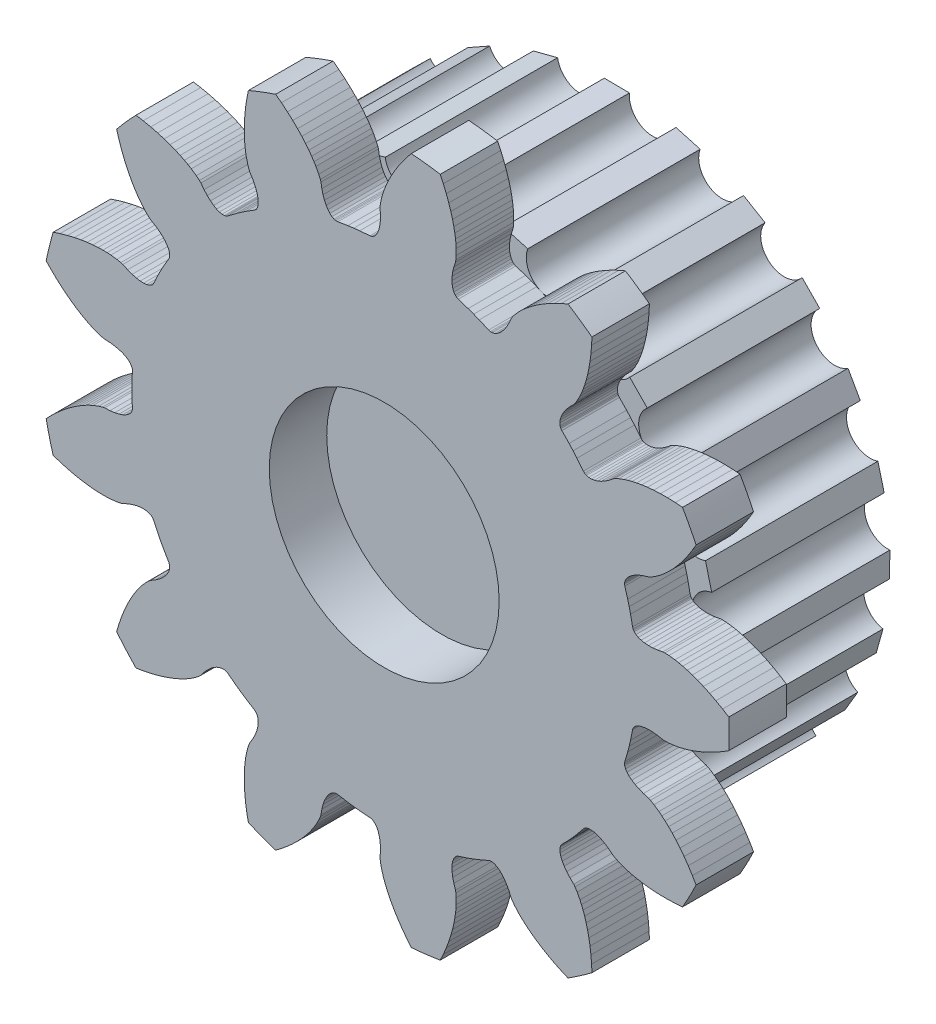
SolidWorks part; units mm, degrees
ref_plane "Front Plane" through (0, 0, 0) normal (0, 0, 1) x (1, 0, 0)
ref_plane "Top Plane" through (0, 0, 0) normal (0, 1, 0) x (1, 0, 0)
ref_plane "Right Plane" through (0, 0, 0) normal (1, 0, 0) x (0, 0, -1)
sketch "Model" plane through (0, 0, 0) normal (0, 0, 1) x (1, 0, 0)
  line L0 (54.9037, -18.3182) -> (55.119, -17.6838)
  line L1 (55.119, -17.6838) -> (55.345, -17.0995)
  line L2 (55.345, -17.0995) -> (55.5777, -16.5655)
  line L3 (55.5777, -16.5655) -> (55.8147, -16.0783)
  line L4 (55.8147, -16.0783) -> (56.0515, -15.6392)
  line L5 (56.0515, -15.6392) -> (56.2838, -15.2487)
  line L6 (56.2838, -15.2487) -> (56.5097, -14.9028)
  line L7 (56.5097, -14.9028) -> (56.7244, -14.6022)
  line L8 (56.7244, -14.6022) -> (56.9247, -14.3453)
  line L9 (56.9247, -14.3453) -> (57.2703, -13.9536)
  line L10 (57.2703, -13.9536) -> (57.526, -13.708)
  line L11 (57.526, -13.708) -> (57.6679, -13.5941)
  line L12 (57.6679, -13.5941) -> (58.066, -13.3611)
  line L13 (58.066, -13.3611) -> (58.4092, -13.1204)
  line L14 (58.4092, -13.1204) -> (58.6978, -12.8763)
  line L15 (58.6978, -12.8763) -> (58.932, -12.6328)
  line L16 (58.932, -12.6328) -> (59.1126, -12.3942)
  line L17 (59.1126, -12.3942) -> (59.2403, -12.1644)
  line L18 (59.2403, -12.1644) -> (59.3164, -11.9475)
  line L19 (59.3164, -11.9475) -> (59.3421, -11.7472)
  line L20 (59.3421, -11.7472) -> (59.3367, -11.6545)
  line L21 (59.3367, -11.6545) -> (59.3192, -11.5674)
  line L22 (59.3192, -11.5674) -> (59.2607, -11.4299)
  line L23 (59.2607, -11.4299) -> (58.8102, -10.6563)
  line L24 (58.8102, -10.6563) -> (58.5642, -10.2007)
  line L25 (58.5642, -10.2007) -> (58.329, -9.7394)
  line L26 (58.329, -9.7394) -> (57.9483, -8.9292)
  line L27 (57.9483, -8.9292) -> (57.8683, -8.8029)
  line L28 (57.8683, -8.8029) -> (57.8065, -8.7391)
  line L29 (57.8065, -8.7391) -> (57.7334, -8.6819)
  line L30 (57.7334, -8.6819) -> (57.5539, -8.5894)
  line L31 (57.5539, -8.5894) -> (57.3321, -8.5288)
  line L32 (57.3321, -8.5288) -> (57.0705, -8.5034)
  line L33 (57.0705, -8.5034) -> (56.7715, -8.5164)
  line L34 (56.7715, -8.5164) -> (56.4381, -8.5709)
  line L35 (56.4381, -8.5709) -> (56.0733, -8.6697)
  line L36 (56.0733, -8.6697) -> (55.6803, -8.8154)
  line L37 (55.6803, -8.8154) -> (55.2623, -9.0107)
  line L38 (55.2623, -9.0107) -> (55.088, -9.0628)
  line L39 (55.088, -9.0628) -> (54.7406, -9.1337)
  line L40 (54.7406, -9.1337) -> (54.2219, -9.1956)
  line L41 (54.2219, -9.1956) -> (53.8967, -9.2145)
  line L42 (53.8967, -9.2145) -> (53.5274, -9.2205)
  line L43 (53.5274, -9.2205) -> (53.1144, -9.2099)
  line L44 (53.1144, -9.2099) -> (52.6611, -9.1792)
  line L45 (52.6611, -9.1792) -> (52.1651, -9.1246)
  line L46 (52.1651, -9.1246) -> (51.6295, -9.0429)
  line L47 (51.6295, -9.0429) -> (51.0579, -8.9311)
  line L48 (51.0579, -8.9311) -> (50.4486, -8.7851)
  line L49 (50.4486, -8.7851) -> (49.8043, -8.6019)
  line L50 (49.8043, -8.6019) -> (49.2012, -8.4037)
  line L51 (48.5945, -5.9424) -> (49.0364, -5.4866)
  line L52 (49.0364, -5.4866) -> (49.5218, -5.0249)
  line L53 (49.5218, -5.0249) -> (49.9935, -4.6126)
  line L54 (49.9935, -4.6126) -> (50.4476, -4.2479)
  line L55 (50.4476, -4.2479) -> (50.8839, -3.9266)
  line L56 (50.8839, -3.9266) -> (51.2977, -3.6479)
  line L57 (51.2977, -3.6479) -> (51.6848, -3.41)
  line L58 (51.6848, -3.41) -> (52.0456, -3.2087)
  line L59 (52.0456, -3.2087) -> (52.3754, -3.0423)
  line L60 (52.3754, -3.0423) -> (52.6721, -2.9079)
  line L61 (52.6721, -2.9079) -> (53.1602, -2.7217)
  line L62 (53.1602, -2.7217) -> (53.5007, -2.623)
  line L63 (53.5007, -2.623) -> (53.6793, -2.5882)
  line L64 (53.6793, -2.5882) -> (54.1401, -2.5668)
  line L65 (54.1401, -2.5668) -> (54.5559, -2.5132)
  line L66 (54.5559, -2.5132) -> (54.9248, -2.4312)
  line L67 (54.9248, -2.4312) -> (55.2454, -2.3245)
  line L68 (55.2454, -2.3245) -> (55.5161, -2.1971)
  line L69 (55.5161, -2.1971) -> (55.736, -2.053)
  line L70 (55.736, -2.053) -> (55.9042, -1.8962)
  line L71 (55.9042, -1.8962) -> (56.0201, -1.7309)
  line L72 (56.0201, -1.7309) -> (56.0583, -1.6463)
  line L73 (56.0583, -1.6463) -> (56.0834, -1.5611)
  line L74 (56.0834, -1.5611) -> (56.0954, -1.4121)
  line L75 (56.0954, -1.4121) -> (56.056, -0.5178)
  line L76 (56.056, -0.5178) -> (56.05, 0)
  line L77 (56.05, 0) -> (56.056, 0.5178)
  line L78 (56.056, 0.5178) -> (56.0954, 1.4121)
  line L79 (56.0954, 1.4121) -> (56.0834, 1.5611)
  line L80 (56.0834, 1.5611) -> (56.0583, 1.6463)
  line L81 (56.0583, 1.6463) -> (56.0201, 1.7309)
  line L82 (56.0201, 1.7309) -> (55.9042, 1.8962)
  line L83 (55.9042, 1.8962) -> (55.736, 2.053)
  line L84 (55.736, 2.053) -> (55.5161, 2.1971)
  line L85 (55.5161, 2.1971) -> (55.2454, 2.3245)
  line L86 (55.2454, 2.3245) -> (54.9248, 2.4312)
  line L87 (54.9248, 2.4312) -> (54.5559, 2.5132)
  line L88 (54.5559, 2.5132) -> (54.1401, 2.5668)
  line L89 (54.1401, 2.5668) -> (53.6793, 2.5882)
  line L90 (53.6793, 2.5882) -> (53.5007, 2.623)
  line L91 (53.5007, 2.623) -> (53.1602, 2.7217)
  line L92 (53.1602, 2.7217) -> (52.6721, 2.9079)
  line L93 (52.6721, 2.9079) -> (52.3754, 3.0423)
  line L94 (52.3754, 3.0423) -> (52.0456, 3.2087)
  line L95 (52.0456, 3.2087) -> (51.6848, 3.41)
  line L96 (51.6848, 3.41) -> (51.2977, 3.6479)
  line L97 (51.2977, 3.6479) -> (50.8839, 3.9266)
  line L98 (50.8839, 3.9266) -> (50.4476, 4.2479)
  line L99 (50.4476, 4.2479) -> (49.9935, 4.6126)
  line L100 (49.9935, 4.6126) -> (49.5218, 5.0249)
  line L101 (49.5218, 5.0249) -> (49.0364, 5.4866)
  line L102 (49.0364, 5.4866) -> (48.5945, 5.9424)
  line L103 (49.2012, 8.4037) -> (49.8043, 8.6019)
  line L104 (49.8043, 8.6019) -> (50.4486, 8.7851)
  line L105 (50.4486, 8.7851) -> (51.0579, 8.9311)
  line L106 (51.0579, 8.9311) -> (51.6295, 9.0429)
  line L107 (51.6295, 9.0429) -> (52.1651, 9.1246)
  line L108 (52.1651, 9.1246) -> (52.6611, 9.1792)
  line L109 (52.6611, 9.1792) -> (53.1144, 9.2099)
  line L110 (53.1144, 9.2099) -> (53.5274, 9.2205)
  line L111 (53.5274, 9.2205) -> (53.8967, 9.2145)
  line L112 (53.8967, 9.2145) -> (54.2219, 9.1956)
  line L113 (54.2219, 9.1956) -> (54.7406, 9.1337)
  line L114 (54.7406, 9.1337) -> (55.088, 9.0628)
  line L115 (55.088, 9.0628) -> (55.2623, 9.0107)
  line L116 (55.2623, 9.0107) -> (55.6803, 8.8154)
  line L117 (55.6803, 8.8154) -> (56.0733, 8.6697)
  line L118 (56.0733, 8.6697) -> (56.4381, 8.5709)
  line L119 (56.4381, 8.5709) -> (56.7715, 8.5164)
  line L120 (56.7715, 8.5164) -> (57.0705, 8.5034)
  line L121 (57.0705, 8.5034) -> (57.3321, 8.5288)
  line L122 (57.3321, 8.5288) -> (57.5539, 8.5894)
  line L123 (57.5539, 8.5894) -> (57.7334, 8.6819)
  line L124 (57.7334, 8.6819) -> (57.8065, 8.7391)
  line L125 (57.8065, 8.7391) -> (57.8683, 8.8029)
  line L126 (57.8683, 8.8029) -> (57.9483, 8.9292)
  line L127 (57.9483, 8.9292) -> (58.329, 9.7394)
  line L128 (58.329, 9.7394) -> (58.5642, 10.2007)
  line L129 (58.5642, 10.2007) -> (58.8102, 10.6563)
  line L130 (58.8102, 10.6563) -> (59.2607, 11.4299)
  line L131 (59.2607, 11.4299) -> (59.3192, 11.5674)
  line L132 (59.3192, 11.5674) -> (59.3367, 11.6545)
  line L133 (59.3367, 11.6545) -> (59.3421, 11.7472)
  line L134 (59.3421, 11.7472) -> (59.3164, 11.9475)
  line L135 (59.3164, 11.9475) -> (59.2403, 12.1644)
  line L136 (59.2403, 12.1644) -> (59.1126, 12.3942)
  line L137 (59.1126, 12.3942) -> (58.932, 12.6328)
  line L138 (58.932, 12.6328) -> (58.6978, 12.8763)
  line L139 (58.6978, 12.8763) -> (58.4092, 13.1204)
  line L140 (58.4092, 13.1204) -> (58.066, 13.3611)
  line L141 (58.066, 13.3611) -> (57.6679, 13.5941)
  line L142 (57.6679, 13.5941) -> (57.526, 13.708)
  line L143 (57.526, 13.708) -> (57.2703, 13.9536)
  line L144 (57.2703, 13.9536) -> (56.9247, 14.3453)
  line L145 (56.9247, 14.3453) -> (56.7244, 14.6022)
  line L146 (56.7244, 14.6022) -> (56.5097, 14.9028)
  line L147 (56.5097, 14.9028) -> (56.2838, 15.2487)
  line L148 (56.2838, 15.2487) -> (56.0515, 15.6392)
  line L149 (56.0515, 15.6392) -> (55.8147, 16.0783)
  line L150 (55.8147, 16.0783) -> (55.5777, 16.5655)
  line L151 (55.5777, 16.5655) -> (55.345, 17.0995)
  line L152 (55.345, 17.0995) -> (55.119, 17.6838)
  line L153 (55.119, 17.6838) -> (54.9037, 18.3182)
  line L154 (54.9037, 18.3182) -> (54.7243, 18.9271)
  line L155 (56.4053, 20.8246) -> (57.0315, 20.7198)
  line L156 (57.0315, 20.7198) -> (57.6871, 20.5826)
  line L157 (57.6871, 20.5826) -> (58.2944, 20.4287)
  line L158 (58.2944, 20.4287) -> (58.8525, 20.2621)
  line L159 (58.8525, 20.2621) -> (59.3648, 20.0855)
  line L160 (59.3648, 20.0855) -> (59.8293, 19.9033)
  line L161 (59.8293, 19.9033) -> (60.2449, 19.7199)
  line L162 (60.2449, 19.7199) -> (60.6155, 19.5373)
  line L163 (60.6155, 19.5373) -> (60.9398, 19.3604)
  line L164 (60.9398, 19.3604) -> (61.219, 19.1925)
  line L165 (61.219, 19.1925) -> (61.6495, 18.8967)
  line L166 (61.6495, 18.8967) -> (61.9241, 18.6724)
  line L167 (61.9241, 18.6724) -> (62.0542, 18.5453)
  line L168 (62.0542, 18.5453) -> (62.3336, 18.1782)
  line L169 (62.3336, 18.1782) -> (62.6139, 17.8664)
  line L170 (62.6139, 17.8664) -> (62.891, 17.6094)
  line L171 (62.891, 17.6094) -> (63.1609, 17.4062)
  line L172 (63.1609, 17.4062) -> (63.4195, 17.2558)
  line L173 (63.4195, 17.2558) -> (63.663, 17.1567)
  line L174 (63.663, 17.1567) -> (63.8876, 17.1073)
  line L175 (63.8876, 17.1073) -> (64.0895, 17.1058)
  line L176 (64.0895, 17.1058) -> (64.1808, 17.1224)
  line L177 (64.1808, 17.1224) -> (64.2652, 17.1503)
  line L178 (64.2652, 17.1503) -> (64.3947, 17.225)
  line L179 (64.3947, 17.225) -> (65.1083, 17.7654)
  line L180 (65.1083, 17.7654) -> (65.531, 18.0645)
  line L181 (65.531, 18.0645) -> (65.9605, 18.3536)
  line L182 (65.9605, 18.3536) -> (66.7189, 18.8292)
  line L183 (66.7189, 18.8292) -> (66.8347, 18.9238)
  line L184 (66.8347, 18.9238) -> (66.8906, 18.9928)
  line L185 (66.8906, 18.9928) -> (66.9385, 19.0724)
  line L186 (66.9385, 19.0724) -> (67.0087, 19.2617)
  line L187 (67.0087, 19.2617) -> (67.0422, 19.4891)
  line L188 (67.0422, 19.4891) -> (67.0359, 19.752)
  line L189 (67.0359, 19.752) -> (66.9869, 20.0471)
  line L190 (66.9869, 20.0471) -> (66.8926, 20.3715)
  line L191 (66.8926, 20.3715) -> (66.7506, 20.7218)
  line L192 (66.7506, 20.7218) -> (66.5585, 21.0944)
  line L193 (66.5585, 21.0944) -> (66.3143, 21.4858)
  line L194 (66.3143, 21.4858) -> (66.2416, 21.6526)
  line L195 (66.2416, 21.6526) -> (66.1293, 21.9888)
  line L196 (66.1293, 21.9888) -> (66.0053, 22.4963)
  line L197 (66.0053, 22.4963) -> (65.9473, 22.8169)
  line L198 (65.9473, 22.8169) -> (65.8969, 23.1828)
  line L199 (65.8969, 23.1828) -> (65.8577, 23.5941)
  line L200 (65.8577, 23.5941) -> (65.8335, 24.0478)
  line L201 (65.8335, 24.0478) -> (65.8278, 24.5467)
  line L202 (65.8278, 24.5467) -> (65.8444, 25.0882)
  line L203 (65.8444, 25.0882) -> (65.8865, 25.6691)
  line L204 (65.8865, 25.6691) -> (65.958, 26.2916)
  line L205 (65.958, 26.2916) -> (66.0622, 26.9533)
  line L206 (66.0622, 26.9533) -> (66.1863, 27.5759)
  line L207 (68.5565, 28.4748) -> (69.0623, 28.0911)
  line L208 (69.0623, 28.0911) -> (69.5791, 27.6649)
  line L209 (69.5791, 27.6649) -> (70.0453, 27.2463)
  line L210 (70.0453, 27.2463) -> (70.462, 26.8395)
  line L211 (70.462, 26.8395) -> (70.8335, 26.4451)
  line L212 (70.8335, 26.4451) -> (71.1601, 26.0679)
  line L213 (71.1601, 26.0679) -> (71.4429, 25.7123)
  line L214 (71.4429, 25.7123) -> (71.6863, 25.3784)
  line L215 (71.6863, 25.3784) -> (71.8911, 25.0711)
  line L216 (71.8911, 25.0711) -> (72.0604, 24.7927)
  line L217 (72.0604, 24.7927) -> (72.3041, 24.3306)
  line L218 (72.3041, 24.3306) -> (72.443, 24.0045)
  line L219 (72.443, 24.0045) -> (72.4991, 23.8314)
  line L220 (72.4991, 23.8314) -> (72.5759, 23.3765)
  line L221 (72.5759, 23.3765) -> (72.6792, 22.9702)
  line L222 (72.6792, 22.9702) -> (72.8051, 22.6139)
  line L223 (72.8051, 22.6139) -> (72.9497, 22.3085)
  line L224 (72.9497, 22.3085) -> (73.1088, 22.0551)
  line L225 (73.1088, 22.0551) -> (73.2784, 21.8542)
  line L226 (73.2784, 21.8542) -> (73.4542, 21.7061)
  line L227 (73.4542, 21.7061) -> (73.6323, 21.611)
  line L228 (73.6323, 21.611) -> (73.7209, 21.5833)
  line L229 (73.7209, 21.5833) -> (73.8085, 21.5687)
  line L230 (73.8085, 21.5687) -> (73.9579, 21.5746)
  line L231 (73.9579, 21.5746) -> (74.841, 21.7216)
  line L232 (74.841, 21.7216) -> (75.3542, 21.79)
  line L233 (75.3542, 21.79) -> (75.8689, 21.8464)
  line L234 (75.8689, 21.8464) -> (76.7615, 21.9151)
  line L235 (76.7615, 21.9151) -> (76.9079, 21.945)
  line L236 (76.9079, 21.945) -> (76.9895, 21.9801)
  line L237 (76.9895, 21.9801) -> (77.0689, 22.0283)
  line L238 (77.0689, 22.0283) -> (77.2191, 22.1633)
  line L239 (77.2191, 22.1633) -> (77.3544, 22.3491)
  line L240 (77.3544, 22.3491) -> (77.4709, 22.5848)
  line L241 (77.4709, 22.5848) -> (77.5648, 22.8689)
  line L242 (77.5648, 22.8689) -> (77.6321, 23.2)
  line L243 (77.6321, 23.2) -> (77.669, 23.5761)
  line L244 (77.669, 23.5761) -> (77.6721, 23.9953)
  line L245 (77.6721, 23.9953) -> (77.6378, 24.4554)
  line L246 (77.6378, 24.4554) -> (77.6509, 24.6368)
  line L247 (77.6509, 24.6368) -> (77.7077, 24.9868)
  line L248 (77.7077, 24.9868) -> (77.8338, 25.4937)
  line L249 (77.8338, 25.4937) -> (77.9314, 25.8045)
  line L250 (77.9314, 25.8045) -> (78.0568, 26.1519)
  line L251 (78.0568, 26.1519) -> (78.2132, 26.5343)
  line L252 (78.2132, 26.5343) -> (78.4026, 26.9473)
  line L253 (78.4026, 26.9473) -> (78.6295, 27.3917)
  line L254 (78.6295, 27.3917) -> (78.8958, 27.8635)
  line L255 (78.8958, 27.8635) -> (79.2031, 28.3583)
  line L256 (79.2031, 28.3583) -> (79.5556, 28.8762)
  line L257 (79.5556, 28.8762) -> (79.9554, 29.4137)
  line L258 (79.9554, 29.4137) -> (80.3546, 29.9073)
  line L259 (82.8711, 29.6018) -> (83.1406, 29.027)
  line L260 (83.1406, 29.027) -> (83.4001, 28.4094)
  line L261 (83.4001, 28.4094) -> (83.6184, 27.8222)
  line L262 (83.6184, 27.8222) -> (83.7984, 27.2683)
  line L263 (83.7984, 27.2683) -> (83.9441, 26.7464)
  line L264 (83.9441, 26.7464) -> (84.058, 26.2606)
  line L265 (84.058, 26.2606) -> (84.1431, 25.8143)
  line L266 (84.1431, 25.8143) -> (84.2034, 25.4056)
  line L267 (84.2034, 25.4056) -> (84.242, 25.0383)
  line L268 (84.242, 25.0383) -> (84.2624, 24.7131)
  line L269 (84.2624, 24.7131) -> (84.2635, 24.1907)
  line L270 (84.2635, 24.1907) -> (84.235, 23.8373)
  line L271 (84.235, 23.8373) -> (84.2043, 23.6581)
  line L272 (84.2043, 23.6581) -> (84.0608, 23.2196)
  line L273 (84.0608, 23.2196) -> (83.9635, 22.8118)
  line L274 (83.9635, 22.8118) -> (83.9094, 22.4377)
  line L275 (83.9094, 22.4377) -> (83.8955, 22.1002)
  line L276 (83.8955, 22.1002) -> (83.9186, 21.8019)
  line L277 (83.9186, 21.8019) -> (83.9753, 21.5452)
  line L278 (83.9753, 21.5452) -> (84.0623, 21.3323)
  line L279 (84.0623, 21.3323) -> (84.1758, 21.1653)
  line L280 (84.1758, 21.1653) -> (84.2413, 21.0996)
  line L281 (84.2413, 21.0996) -> (84.3121, 21.046)
  line L282 (84.3121, 21.046) -> (84.4472, 20.9818)
  line L283 (84.4472, 20.9818) -> (85.2973, 20.7016)
  line L284 (85.2973, 20.7016) -> (85.7836, 20.5236)
  line L285 (85.7836, 20.5236) -> (86.2655, 20.3344)
  line L286 (86.2655, 20.3344) -> (87.0878, 19.9804)
  line L287 (87.0878, 19.9804) -> (87.2314, 19.9389)
  line L288 (87.2314, 19.9389) -> (87.3199, 19.932)
  line L289 (87.3199, 19.932) -> (87.4126, 19.9378)
  line L290 (87.4126, 19.9378) -> (87.6083, 19.9875)
  line L291 (87.6083, 19.9875) -> (87.8145, 20.0892)
  line L292 (87.8145, 20.0892) -> (88.0272, 20.2437)
  line L293 (88.0272, 20.2437) -> (88.2423, 20.4517)
  line L294 (88.2423, 20.4517) -> (88.4558, 20.7135)
  line L295 (88.4558, 20.7135) -> (88.6633, 21.0294)
  line L296 (88.6633, 21.0294) -> (88.8609, 21.3992)
  line L297 (88.8609, 21.3992) -> (89.0442, 21.8225)
  line L298 (89.0442, 21.8225) -> (89.1401, 21.9771)
  line L299 (89.1401, 21.9771) -> (89.3531, 22.2605)
  line L300 (89.3531, 22.2605) -> (89.7003, 22.6508)
  line L301 (89.7003, 22.6508) -> (89.9312, 22.8806)
  line L302 (89.9312, 22.8806) -> (90.2037, 23.13)
  line L303 (90.2037, 23.13) -> (90.5199, 23.3959)
  line L304 (90.5199, 23.3959) -> (90.8796, 23.6735)
  line L305 (90.8796, 23.6735) -> (91.2869, 23.9616)
  line L306 (91.2869, 23.9616) -> (91.742, 24.2556)
  line L307 (91.742, 24.2556) -> (92.2441, 24.5509)
  line L308 (92.2441, 24.5509) -> (92.7969, 24.8457)
  line L309 (92.7969, 24.8457) -> (93.4007, 25.1359)
  line L310 (93.4007, 25.1359) -> (93.9836, 25.3874)
  line L311 (96.0698, 23.9474) -> (96.0413, 23.3132)
  line L312 (96.0413, 23.3132) -> (95.9841, 22.6457)
  line L313 (95.9841, 22.6457) -> (95.9045, 22.0243)
  line L314 (95.9045, 22.0243) -> (95.8064, 21.4502)
  line L315 (95.8064, 21.4502) -> (95.6929, 20.9204)
  line L316 (95.6929, 20.9204) -> (95.568, 20.4373)
  line L317 (95.568, 20.4373) -> (95.4359, 20.0026)
  line L318 (95.4359, 20.0026) -> (95.2994, 19.6127)
  line L319 (95.2994, 19.6127) -> (95.1629, 19.2695)
  line L320 (95.1629, 19.2695) -> (95.0299, 18.9721)
  line L321 (95.0299, 18.9721) -> (94.7881, 18.509)
  line L322 (94.7881, 18.509) -> (94.5986, 18.2094)
  line L323 (94.5986, 18.2094) -> (94.488, 18.0649)
  line L324 (94.488, 18.0649) -> (94.1573, 17.7433)
  line L325 (94.1573, 17.7433) -> (93.8816, 17.4275)
  line L326 (93.8816, 17.4275) -> (93.6598, 17.1214)
  line L327 (93.6598, 17.1214) -> (93.4907, 16.829)
  line L328 (93.4907, 16.829) -> (93.3725, 16.5541)
  line L329 (93.3725, 16.5541) -> (93.3035, 16.3004)
  line L330 (93.3035, 16.3004) -> (93.2815, 16.0716)
  line L331 (93.2815, 16.0716) -> (93.3044, 15.871)
  line L332 (93.3044, 15.871) -> (93.3319, 15.7823)
  line L333 (93.3319, 15.7823) -> (93.3697, 15.7019)
  line L334 (93.3697, 15.7019) -> (93.4594, 15.5824)
  line L335 (93.4594, 15.5824) -> (94.082, 14.9391)
  line L336 (94.082, 14.9391) -> (94.4298, 14.5555)
  line L337 (94.4298, 14.5555) -> (94.7686, 14.164)
  line L338 (94.7686, 14.164) -> (95.3322, 13.4685)
  line L339 (95.3322, 13.4685) -> (95.44, 13.3649)
  line L340 (95.44, 13.3649) -> (95.5153, 13.3178)
  line L341 (95.5153, 13.3178) -> (95.6, 13.2798)
  line L342 (95.6, 13.2798) -> (95.7964, 13.2329)
  line L343 (95.7964, 13.2329) -> (96.0262, 13.2271)
  line L344 (96.0262, 13.2271) -> (96.2864, 13.265)
  line L345 (96.2864, 13.265) -> (96.5735, 13.3492)
  line L346 (96.5735, 13.3492) -> (96.8842, 13.4819)
  line L347 (96.8842, 13.4819) -> (97.2147, 13.6651)
  line L348 (97.2147, 13.6651) -> (97.5615, 13.9007)
  line L349 (97.5615, 13.9007) -> (97.9206, 14.1903)
  line L350 (97.9206, 14.1903) -> (98.0774, 14.2826)
  line L351 (98.0774, 14.2826) -> (98.3977, 14.4346)
  line L352 (98.3977, 14.4346) -> (98.8865, 14.6189)
  line L353 (98.8865, 14.6189) -> (99.1977, 14.7151)
  line L354 (99.1977, 14.7151) -> (99.5549, 14.8092)
  line L355 (99.5549, 14.8092) -> (99.9585, 14.8978)
  line L356 (99.9585, 14.8978) -> (100.4059, 14.9764)
  line L357 (100.4059, 14.9764) -> (100.9005, 15.0422)
  line L358 (100.9005, 15.0422) -> (101.4401, 15.091)
  line L359 (101.4401, 15.091) -> (102.0219, 15.1192)
  line L360 (102.0219, 15.1192) -> (102.6484, 15.1233)
  line L361 (102.6484, 15.1233) -> (103.3178, 15.0997)
  line L362 (103.3178, 15.0997) -> (103.9508, 15.0515)
  line L363 (105.1289, 12.8069) -> (104.8089, 12.2586)
  line L364 (104.8089, 12.2586) -> (104.4481, 11.6942)
  line L365 (104.4481, 11.6942) -> (104.0888, 11.1809)
  line L366 (104.0888, 11.1809) -> (103.7352, 10.7182)
  line L367 (103.7352, 10.7182) -> (103.3885, 10.3018)
  line L368 (103.3885, 10.3018) -> (103.0534, 9.9321)
  line L369 (103.0534, 9.9321) -> (102.7344, 9.6086)
  line L370 (102.7344, 9.6086) -> (102.4323, 9.3267)
  line L371 (102.4323, 9.3267) -> (102.1519, 9.0863)
  line L372 (102.1519, 9.0863) -> (101.896, 8.8848)
  line L373 (101.896, 8.8848) -> (101.4667, 8.5871)
  line L374 (101.4667, 8.5871) -> (101.1596, 8.4099)
  line L375 (101.1596, 8.4099) -> (100.9946, 8.3333)
  line L376 (100.9946, 8.3333) -> (100.5523, 8.2023)
  line L377 (100.5523, 8.2023) -> (100.1614, 8.0508)
  line L378 (100.1614, 8.0508) -> (99.8228, 7.8828)
  line L379 (99.8228, 7.8828) -> (99.5371, 7.7025)
  line L380 (99.5371, 7.7025) -> (99.3047, 7.514)
  line L381 (99.3047, 7.514) -> (99.1257, 7.3215)
  line L382 (99.1257, 7.3215) -> (98.9999, 7.129)
  line L383 (98.9999, 7.129) -> (98.927, 6.9407)
  line L384 (98.927, 6.9407) -> (98.9101, 6.8494)
  line L385 (98.9101, 6.8494) -> (98.9062, 6.7607)
  line L386 (98.9062, 6.7607) -> (98.9301, 6.6131)
  line L387 (98.9301, 6.6131) -> (99.1824, 5.7542)
  line L388 (99.1824, 5.7542) -> (99.3122, 5.253)
  line L389 (99.3122, 5.253) -> (99.4302, 4.7488)
  line L390 (99.4302, 4.7488) -> (99.606, 3.8711)
  line L391 (99.606, 3.8711) -> (99.6534, 3.7293)
  line L392 (99.6534, 3.7293) -> (99.6981, 3.6525)
  line L393 (99.6981, 3.6525) -> (99.7554, 3.5795)
  line L394 (99.7554, 3.5795) -> (99.9075, 3.4467)
  line L395 (99.9075, 3.4467) -> (100.1084, 3.3348)
  line L396 (100.1084, 3.3348) -> (100.3563, 3.2475)
  line L397 (100.3563, 3.2475) -> (100.6497, 3.1886)
  line L398 (100.6497, 3.1886) -> (100.9864, 3.1617)
  line L399 (100.9864, 3.1617) -> (101.3643, 3.1703)
  line L400 (101.3643, 3.1703) -> (101.7808, 3.2178)
  line L401 (101.7808, 3.2178) -> (102.2334, 3.3073)
  line L402 (102.2334, 3.3073) -> (102.4151, 3.3162)
  line L403 (102.4151, 3.3162) -> (102.7693, 3.302)
  line L404 (102.7693, 3.302) -> (103.2878, 3.238)
  line L405 (103.2878, 3.238) -> (103.6081, 3.1784)
  line L406 (103.6081, 3.1784) -> (103.9681, 3.0959)
  line L407 (103.9681, 3.0959) -> (104.3666, 2.9867)
  line L408 (104.3666, 2.9867) -> (104.7993, 2.8484)
  line L409 (104.7993, 2.8484) -> (105.2679, 2.6768)
  line L410 (105.2679, 2.6768) -> (105.7684, 2.4693)
  line L411 (105.7684, 2.4693) -> (106.2966, 2.2239)
  line L412 (106.2966, 2.2239) -> (106.8532, 1.9364)
  line L413 (106.8532, 1.9364) -> (107.435, 1.6043)
  line L414 (107.435, 1.6043) -> (107.9731, 1.2675)
  line L415 (107.9731, -1.2675) -> (107.435, -1.6043)
  line L416 (107.435, -1.6043) -> (106.8532, -1.9364)
  line L417 (106.8532, -1.9364) -> (106.2966, -2.2239)
  line L418 (106.2966, -2.2239) -> (105.7684, -2.4693)
  line L419 (105.7684, -2.4693) -> (105.2679, -2.6768)
  line L420 (105.2679, -2.6768) -> (104.7993, -2.8484)
  line L421 (104.7993, -2.8484) -> (104.3666, -2.9867)
  line L422 (104.3666, -2.9867) -> (103.9681, -3.0959)
  line L423 (103.9681, -3.0959) -> (103.6081, -3.1784)
  line L424 (103.6081, -3.1784) -> (103.2878, -3.238)
  line L425 (103.2878, -3.238) -> (102.7693, -3.302)
  line L426 (102.7693, -3.302) -> (102.4151, -3.3162)
  line L427 (102.4151, -3.3162) -> (102.2334, -3.3073)
  line L428 (102.2334, -3.3073) -> (101.7808, -3.2178)
  line L429 (101.7808, -3.2178) -> (101.3643, -3.1703)
  line L430 (101.3643, -3.1703) -> (100.9864, -3.1617)
  line L431 (100.9864, -3.1617) -> (100.6497, -3.1886)
  line L432 (100.6497, -3.1886) -> (100.3563, -3.2475)
  line L433 (100.3563, -3.2475) -> (100.1084, -3.3348)
  line L434 (100.1084, -3.3348) -> (99.9075, -3.4467)
  line L435 (99.9075, -3.4467) -> (99.7554, -3.5795)
  line L436 (99.7554, -3.5795) -> (99.6981, -3.6525)
  line L437 (99.6981, -3.6525) -> (99.6534, -3.7293)
  line L438 (99.6534, -3.7293) -> (99.606, -3.8711)
  line L439 (99.606, -3.8711) -> (99.4302, -4.7488)
  line L440 (99.4302, -4.7488) -> (99.3122, -5.253)
  line L441 (99.3122, -5.253) -> (99.1824, -5.7542)
  line L442 (99.1824, -5.7542) -> (98.9301, -6.6131)
  line L443 (98.9301, -6.6131) -> (98.9062, -6.7607)
  line L444 (98.9062, -6.7607) -> (98.9101, -6.8494)
  line L445 (98.9101, -6.8494) -> (98.927, -6.9407)
  line L446 (98.927, -6.9407) -> (98.9999, -7.129)
  line L447 (98.9999, -7.129) -> (99.1257, -7.3215)
  line L448 (99.1257, -7.3215) -> (99.3047, -7.514)
  line L449 (99.3047, -7.514) -> (99.5371, -7.7025)
  line L450 (99.5371, -7.7025) -> (99.8228, -7.8828)
  line L451 (99.8228, -7.8828) -> (100.1614, -8.0508)
  line L452 (100.1614, -8.0508) -> (100.5523, -8.2023)
  line L453 (100.5523, -8.2023) -> (100.9946, -8.3333)
  line L454 (100.9946, -8.3333) -> (101.1596, -8.4099)
  line L455 (101.1596, -8.4099) -> (101.4667, -8.5871)
  line L456 (101.4667, -8.5871) -> (101.896, -8.8848)
  line L457 (101.896, -8.8848) -> (102.1519, -9.0863)
  line L458 (102.1519, -9.0863) -> (102.4323, -9.3267)
  line L459 (102.4323, -9.3267) -> (102.7344, -9.6086)
  line L460 (102.7344, -9.6086) -> (103.0534, -9.9321)
  line L461 (103.0534, -9.9321) -> (103.3885, -10.3018)
  line L462 (103.3885, -10.3018) -> (103.7352, -10.7182)
  line L463 (103.7352, -10.7182) -> (104.0888, -11.1809)
  line L464 (104.0888, -11.1809) -> (104.4481, -11.6942)
  line L465 (104.4481, -11.6942) -> (104.8089, -12.2586)
  line L466 (104.8089, -12.2586) -> (105.1289, -12.8069)
  line L467 (103.9508, -15.0515) -> (103.3178, -15.0997)
  line L468 (103.3178, -15.0997) -> (102.6484, -15.1233)
  line L469 (102.6484, -15.1233) -> (102.0219, -15.1192)
  line L470 (102.0219, -15.1192) -> (101.4401, -15.091)
  line L471 (101.4401, -15.091) -> (100.9005, -15.0422)
  line L472 (100.9005, -15.0422) -> (100.4059, -14.9764)
  line L473 (100.4059, -14.9764) -> (99.9585, -14.8978)
  line L474 (99.9585, -14.8978) -> (99.5549, -14.8092)
  line L475 (99.5549, -14.8092) -> (99.1977, -14.7151)
  line L476 (99.1977, -14.7151) -> (98.8865, -14.6189)
  line L477 (98.8865, -14.6189) -> (98.3977, -14.4346)
  line L478 (98.3977, -14.4346) -> (98.0774, -14.2826)
  line L479 (98.0774, -14.2826) -> (97.9206, -14.1903)
  line L480 (97.9206, -14.1903) -> (97.5615, -13.9007)
  line L481 (97.5615, -13.9007) -> (97.2147, -13.6651)
  line L482 (97.2147, -13.6651) -> (96.8842, -13.4819)
  line L483 (96.8842, -13.4819) -> (96.5735, -13.3492)
  line L484 (96.5735, -13.3492) -> (96.2864, -13.265)
  line L485 (96.2864, -13.265) -> (96.0262, -13.2271)
  line L486 (96.0262, -13.2271) -> (95.7964, -13.2329)
  line L487 (95.7964, -13.2329) -> (95.6, -13.2798)
  line L488 (95.6, -13.2798) -> (95.5153, -13.3178)
  line L489 (95.5153, -13.3178) -> (95.44, -13.3649)
  line L490 (95.44, -13.3649) -> (95.3322, -13.4685)
  line L491 (95.3322, -13.4685) -> (94.7686, -14.164)
  line L492 (94.7686, -14.164) -> (94.4298, -14.5555)
  line L493 (94.4298, -14.5555) -> (94.082, -14.9391)
  line L494 (94.082, -14.9391) -> (93.4594, -15.5824)
  line L495 (93.4594, -15.5824) -> (93.3697, -15.7019)
  line L496 (93.3697, -15.7019) -> (93.3319, -15.7823)
  line L497 (93.3319, -15.7823) -> (93.3044, -15.871)
  line L498 (93.3044, -15.871) -> (93.2815, -16.0716)
  line L499 (93.2815, -16.0716) -> (93.3035, -16.3004)
  line L500 (93.3035, -16.3004) -> (93.3725, -16.5541)
  line L501 (93.3725, -16.5541) -> (93.4907, -16.829)
  line L502 (93.4907, -16.829) -> (93.6598, -17.1214)
  line L503 (93.6598, -17.1214) -> (93.8816, -17.4275)
  line L504 (93.8816, -17.4275) -> (94.1573, -17.7433)
  line L505 (94.1573, -17.7433) -> (94.488, -18.0649)
  line L506 (94.488, -18.0649) -> (94.5986, -18.2094)
  line L507 (94.5986, -18.2094) -> (94.7881, -18.509)
  line L508 (94.7881, -18.509) -> (95.0299, -18.9721)
  line L509 (95.0299, -18.9721) -> (95.1629, -19.2695)
  line L510 (95.1629, -19.2695) -> (95.2994, -19.6127)
  line L511 (95.2994, -19.6127) -> (95.4359, -20.0026)
  line L512 (95.4359, -20.0026) -> (95.568, -20.4373)
  line L513 (95.568, -20.4373) -> (95.6929, -20.9204)
  line L514 (95.6929, -20.9204) -> (95.8064, -21.4502)
  line L515 (95.8064, -21.4502) -> (95.9045, -22.0243)
  line L516 (95.9045, -22.0243) -> (95.9841, -22.6457)
  line L517 (95.9841, -22.6457) -> (96.0413, -23.3132)
  line L518 (96.0413, -23.3132) -> (96.0698, -23.9474)
  line L519 (93.9836, -25.3874) -> (93.4007, -25.1359)
  line L520 (93.4007, -25.1359) -> (92.7969, -24.8457)
  line L521 (92.7969, -24.8457) -> (92.2441, -24.5509)
  line L522 (92.2441, -24.5509) -> (91.742, -24.2556)
  line L523 (91.742, -24.2556) -> (91.2869, -23.9616)
  line L524 (91.2869, -23.9616) -> (90.8796, -23.6735)
  line L525 (90.8796, -23.6735) -> (90.5199, -23.3959)
  line L526 (90.5199, -23.3959) -> (90.2037, -23.13)
  line L527 (90.2037, -23.13) -> (89.9312, -22.8806)
  line L528 (89.9312, -22.8806) -> (89.7003, -22.6508)
  line L529 (89.7003, -22.6508) -> (89.3531, -22.2605)
  line L530 (89.3531, -22.2605) -> (89.1401, -21.9771)
  line L531 (89.1401, -21.9771) -> (89.0442, -21.8225)
  line L532 (89.0442, -21.8225) -> (88.8609, -21.3992)
  line L533 (88.8609, -21.3992) -> (88.6633, -21.0294)
  line L534 (88.6633, -21.0294) -> (88.4558, -20.7135)
  line L535 (88.4558, -20.7135) -> (88.2423, -20.4517)
  line L536 (88.2423, -20.4517) -> (88.0272, -20.2437)
  line L537 (88.0272, -20.2437) -> (87.8145, -20.0892)
  line L538 (87.8145, -20.0892) -> (87.6083, -19.9875)
  line L539 (87.6083, -19.9875) -> (87.4126, -19.9378)
  line L540 (87.4126, -19.9378) -> (87.3199, -19.932)
  line L541 (87.3199, -19.932) -> (87.2314, -19.9389)
  line L542 (87.2314, -19.9389) -> (87.0878, -19.9804)
  line L543 (87.0878, -19.9804) -> (86.2655, -20.3344)
  line L544 (86.2655, -20.3344) -> (85.7836, -20.5236)
  line L545 (85.7836, -20.5236) -> (85.2973, -20.7016)
  line L546 (85.2973, -20.7016) -> (84.4472, -20.9818)
  line L547 (84.4472, -20.9818) -> (84.3121, -21.046)
  line L548 (84.3121, -21.046) -> (84.2413, -21.0996)
  line L549 (84.2413, -21.0996) -> (84.1758, -21.1653)
  line L550 (84.1758, -21.1653) -> (84.0623, -21.3323)
  line L551 (84.0623, -21.3323) -> (83.9753, -21.5452)
  line L552 (83.9753, -21.5452) -> (83.9186, -21.8019)
  line L553 (83.9186, -21.8019) -> (83.8955, -22.1002)
  line L554 (83.8955, -22.1002) -> (83.9094, -22.4377)
  line L555 (83.9094, -22.4377) -> (83.9635, -22.8118)
  line L556 (83.9635, -22.8118) -> (84.0608, -23.2196)
  line L557 (84.0608, -23.2196) -> (84.2043, -23.6581)
  line L558 (84.2043, -23.6581) -> (84.235, -23.8373)
  line L559 (84.235, -23.8373) -> (84.2635, -24.1907)
  line L560 (84.2635, -24.1907) -> (84.2624, -24.7131)
  line L561 (84.2624, -24.7131) -> (84.242, -25.0383)
  line L562 (84.242, -25.0383) -> (84.2034, -25.4056)
  line L563 (84.2034, -25.4056) -> (84.1431, -25.8143)
  line L564 (84.1431, -25.8143) -> (84.058, -26.2606)
  line L565 (84.058, -26.2606) -> (83.9441, -26.7464)
  line L566 (83.9441, -26.7464) -> (83.7984, -27.2683)
  line L567 (83.7984, -27.2683) -> (83.6184, -27.8222)
  line L568 (83.6184, -27.8222) -> (83.4001, -28.4094)
  line L569 (83.4001, -28.4094) -> (83.1406, -29.027)
  line L570 (83.1406, -29.027) -> (82.8711, -29.6018)
  line L571 (80.3546, -29.9073) -> (79.9554, -29.4137)
  line L572 (79.9554, -29.4137) -> (79.5556, -28.8762)
  line L573 (79.5556, -28.8762) -> (79.2031, -28.3583)
  line L574 (79.2031, -28.3583) -> (78.8958, -27.8635)
  line L575 (78.8958, -27.8635) -> (78.6295, -27.3917)
  line L576 (78.6295, -27.3917) -> (78.4026, -26.9473)
  line L577 (78.4026, -26.9473) -> (78.2132, -26.5343)
  line L578 (78.2132, -26.5343) -> (78.0568, -26.1519)
  line L579 (78.0568, -26.1519) -> (77.9314, -25.8045)
  line L580 (77.9314, -25.8045) -> (77.8338, -25.4937)
  line L581 (77.8338, -25.4937) -> (77.7077, -24.9868)
  line L582 (77.7077, -24.9868) -> (77.6509, -24.6368)
  line L583 (77.6509, -24.6368) -> (77.6378, -24.4554)
  line L584 (77.6378, -24.4554) -> (77.6721, -23.9953)
  line L585 (77.6721, -23.9953) -> (77.669, -23.5761)
  line L586 (77.669, -23.5761) -> (77.6321, -23.2)
  line L587 (77.6321, -23.2) -> (77.5648, -22.8689)
  line L588 (77.5648, -22.8689) -> (77.4709, -22.5848)
  line L589 (77.4709, -22.5848) -> (77.3544, -22.3491)
  line L590 (77.3544, -22.3491) -> (77.2191, -22.1633)
  line L591 (77.2191, -22.1633) -> (77.0689, -22.0283)
  line L592 (77.0689, -22.0283) -> (76.9895, -21.9801)
  line L593 (76.9895, -21.9801) -> (76.9079, -21.945)
  line L594 (76.9079, -21.945) -> (76.7615, -21.9151)
  line L595 (76.7615, -21.9151) -> (75.8689, -21.8464)
  line L596 (75.8689, -21.8464) -> (75.3542, -21.79)
  line L597 (75.3542, -21.79) -> (74.841, -21.7216)
  line L598 (74.841, -21.7216) -> (73.9579, -21.5746)
  line L599 (73.9579, -21.5746) -> (73.8085, -21.5687)
  line L600 (73.8085, -21.5687) -> (73.7209, -21.5833)
  line L601 (73.7209, -21.5833) -> (73.6323, -21.611)
  line L602 (73.6323, -21.611) -> (73.4542, -21.7061)
  line L603 (73.4542, -21.7061) -> (73.2784, -21.8542)
  line L604 (73.2784, -21.8542) -> (73.1088, -22.0551)
  line L605 (73.1088, -22.0551) -> (72.9497, -22.3085)
  line L606 (72.9497, -22.3085) -> (72.8051, -22.6139)
  line L607 (72.8051, -22.6139) -> (72.6792, -22.9702)
  line L608 (72.6792, -22.9702) -> (72.5759, -23.3765)
  line L609 (72.5759, -23.3765) -> (72.4991, -23.8314)
  line L610 (72.4991, -23.8314) -> (72.443, -24.0045)
  line L611 (72.443, -24.0045) -> (72.3041, -24.3306)
  line L612 (72.3041, -24.3306) -> (72.0604, -24.7927)
  line L613 (72.0604, -24.7927) -> (71.8911, -25.0711)
  line L614 (71.8911, -25.0711) -> (71.6863, -25.3784)
  line L615 (71.6863, -25.3784) -> (71.4429, -25.7123)
  line L616 (71.4429, -25.7123) -> (71.1601, -26.0679)
  line L617 (71.1601, -26.0679) -> (70.8335, -26.4451)
  line L618 (70.8335, -26.4451) -> (70.462, -26.8395)
  line L619 (70.462, -26.8395) -> (70.0453, -27.2463)
  line L620 (70.0453, -27.2463) -> (69.5791, -27.6649)
  line L621 (69.5791, -27.6649) -> (69.0623, -28.0911)
  line L622 (69.0623, -28.0911) -> (68.5565, -28.4748)
  line L623 (66.1863, -27.5759) -> (66.0622, -26.9533)
  line L624 (66.0622, -26.9533) -> (65.958, -26.2916)
  line L625 (65.958, -26.2916) -> (65.8865, -25.6691)
  line L626 (65.8865, -25.6691) -> (65.8444, -25.0882)
  line L627 (65.8444, -25.0882) -> (65.8278, -24.5467)
  line L628 (65.8278, -24.5467) -> (65.8335, -24.0478)
  line L629 (65.8335, -24.0478) -> (65.8577, -23.5941)
  line L630 (65.8577, -23.5941) -> (65.8969, -23.1828)
  line L631 (65.8969, -23.1828) -> (65.9473, -22.8169)
  line L632 (65.9473, -22.8169) -> (66.0053, -22.4963)
  line L633 (66.0053, -22.4963) -> (66.1293, -21.9888)
  line L634 (66.1293, -21.9888) -> (66.2416, -21.6526)
  line L635 (66.2416, -21.6526) -> (66.3143, -21.4858)
  line L636 (66.3143, -21.4858) -> (66.5585, -21.0944)
  line L637 (66.5585, -21.0944) -> (66.7506, -20.7218)
  line L638 (66.7506, -20.7218) -> (66.8926, -20.3715)
  line L639 (66.8926, -20.3715) -> (66.9869, -20.0471)
  line L640 (66.9869, -20.0471) -> (67.0359, -19.752)
  line L641 (67.0359, -19.752) -> (67.0422, -19.4891)
  line L642 (67.0422, -19.4891) -> (67.0087, -19.2617)
  line L643 (67.0087, -19.2617) -> (66.9385, -19.0724)
  line L644 (66.9385, -19.0724) -> (66.8906, -18.9928)
  line L645 (66.8906, -18.9928) -> (66.8347, -18.9238)
  line L646 (66.8347, -18.9238) -> (66.7189, -18.8292)
  line L647 (66.7189, -18.8292) -> (65.9605, -18.3536)
  line L648 (65.9605, -18.3536) -> (65.531, -18.0645)
  line L649 (65.531, -18.0645) -> (65.1083, -17.7654)
  line L650 (65.1083, -17.7654) -> (64.3947, -17.225)
  line L651 (64.3947, -17.225) -> (64.2652, -17.1503)
  line L652 (64.2652, -17.1503) -> (64.1808, -17.1224)
  line L653 (64.1808, -17.1224) -> (64.0895, -17.1058)
  line L654 (64.0895, -17.1058) -> (63.8876, -17.1073)
  line L655 (63.8876, -17.1073) -> (63.663, -17.1567)
  line L656 (63.663, -17.1567) -> (63.4195, -17.2558)
  line L657 (63.4195, -17.2558) -> (63.1609, -17.4062)
  line L658 (63.1609, -17.4062) -> (62.891, -17.6094)
  line L659 (62.891, -17.6094) -> (62.6139, -17.8664)
  line L660 (62.6139, -17.8664) -> (62.3336, -18.1782)
  line L661 (62.3336, -18.1782) -> (62.0542, -18.5453)
  line L662 (62.0542, -18.5453) -> (61.9241, -18.6724)
  line L663 (61.9241, -18.6724) -> (61.6495, -18.8967)
  line L664 (61.6495, -18.8967) -> (61.219, -19.1925)
  line L665 (61.219, -19.1925) -> (60.9398, -19.3604)
  line L666 (60.9398, -19.3604) -> (60.6155, -19.5373)
  line L667 (60.6155, -19.5373) -> (60.2449, -19.7199)
  line L668 (60.2449, -19.7199) -> (59.8293, -19.9033)
  line L669 (59.8293, -19.9033) -> (59.3648, -20.0855)
  line L670 (59.3648, -20.0855) -> (58.8525, -20.2621)
  line L671 (58.8525, -20.2621) -> (58.2944, -20.4287)
  line L672 (58.2944, -20.4287) -> (57.6871, -20.5826)
  line L673 (57.6871, -20.5826) -> (57.0315, -20.7198)
  line L674 (57.0315, -20.7198) -> (56.4053, -20.8246)
  line L675 (54.7243, -18.9271) -> (54.9037, -18.3182)
  circle A1 centre (78, 0) radius 0.75
  arc A2 (48.5945, -5.9424) -> (49.2012, -8.4037) centre (78.0001, 0) ccw
  arc A3 (49.2012, 8.4037) -> (48.5945, 5.9424) centre (78.0001, 0) ccw
  arc A4 (56.4053, 20.8246) -> (54.7243, 18.9271) centre (78.0001, -0.0001) ccw
  arc A5 (68.5565, 28.4748) -> (66.1863, 27.5759) centre (78, -0.0001) ccw
  arc A6 (82.8711, 29.6018) -> (80.3546, 29.9073) centre (78, -0.0001) ccw
  arc A7 (96.0698, 23.9474) -> (93.9836, 25.3874) centre (77.9999, -0.0001) ccw
  arc A8 (105.1289, 12.8069) -> (103.9508, 15.0515) centre (77.9999, -0.0001) ccw
  arc A9 (107.9731, -1.2675) -> (107.9731, 1.2675) centre (77.9999, 0) ccw
  arc A10 (103.9508, -15.0515) -> (105.1289, -12.8069) centre (77.9999, 0.0001) ccw
  arc A11 (93.9836, -25.3874) -> (96.0698, -23.9474) centre (77.9999, 0.0001) ccw
  arc A12 (80.3546, -29.9073) -> (82.8711, -29.6018) centre (78, 0.0001) ccw
  arc A13 (66.1863, -27.5759) -> (68.5565, -28.4748) centre (78, 0.0001) ccw
  arc A14 (54.7243, -18.9271) -> (56.4053, -20.8246) centre (78.0001, 0.0001) ccw
  arc A22 (107.9731, -1.2675) -> (107.9731, 1.2675) centre (77.9999, 0) ccw
extrude "Boss-Extrude2" add sketch "Model" along normal blind 5 contours L675 A14 L674 L673 L672 L671 L670 L669 L668 L667 L666 L665 L664 L663 L662 L661 L660 L659 L658 L657 L656 L655 L654 L653 L652 L651 L650 L649 L648 L647 L646 L645 L644 L643 L642 L641 L640 L639 L638 L637 L636 L635 L634 L633 L632 L631 L630 L629 L628 L627 L626 region at (55.8097, -18.2719, 0)
sketch "Sketch3" plane through (0, 0, 0) normal (0, 0, -1) x (-1, 0, 0)
  circle A0 centre (-78, 0) radius 10
  dimension "D1" = 20
extrude "Cut-Extrude1" cut sketch "Sketch3" against normal blind 5
sketch "Sketch4" plane through (0, 0, 0) normal (0, 0, -1) x (-1, 0, 0)
  line L0 (-79.3319, 23.963) -> (-77.1509, 23.985)
  line L1 (-73.0845, 23.4912) -> (-70.972, 22.9479)
  line L2 (-67.172, 21.4185) -> (-65.2721, 20.347)
  line L3 (-61.9974, 17.8862) -> (-60.4396, 16.3595)
  line L4 (-57.9134, 13.135) -> (-56.8038, 11.2571)
  line L5 (-55.1982, 7.4886) -> (-54.6125, 5.3876)
  line L6 (-54.037, 1.3319) -> (-54.015, -0.8491)
  line L7 (-54.5088, -4.9155) -> (-55.0521, -7.028)
  line L8 (-56.5815, -10.828) -> (-57.653, -12.7279)
  line L9 (-60.1138, -16.0026) -> (-61.6405, -17.5604)
  line L10 (-64.865, -20.0866) -> (-66.7429, -21.1962)
  line L11 (-70.5114, -22.8018) -> (-72.6124, -23.3875)
  line L12 (-76.6681, -23.963) -> (-78.8491, -23.985)
  line L13 (-82.9155, -23.4912) -> (-85.028, -22.9479)
  line L14 (-88.828, -21.4185) -> (-90.7279, -20.347)
  line L15 (-94.0026, -17.8862) -> (-95.5604, -16.3595)
  line L16 (-98.0866, -13.135) -> (-99.1962, -11.2571)
  line L17 (-100.8018, -7.4886) -> (-101.3875, -5.3876)
  line L18 (-101.963, -1.3319) -> (-101.985, 0.8491)
  line L19 (-101.4912, 4.9155) -> (-100.9479, 7.028)
  line L20 (-99.4185, 10.828) -> (-98.347, 12.7279)
  line L21 (-95.8862, 16.0026) -> (-94.3595, 17.5604)
  line L22 (-91.135, 20.0866) -> (-89.2571, 21.1962)
  line L23 (-85.4886, 22.8018) -> (-83.3876, 23.3875)
  circle A1 centre (-78, 0) radius 24 construction
  circle A2 centre (-75.3542, 21.79) radius 2.05 construction
  circle A3 centre (-75.1071, 23.825) radius 2.05
  circle A4 centre (-69.0393, 22.2645) radius 2.05
  circle A5 centre (-63.5822, 19.1866) radius 2.05
  circle A6 centre (-59.1076, 14.8013) radius 2.05
  circle A7 centre (-55.9205, 9.4072) radius 2.05
  circle A8 centre (-54.2381, 3.3721) radius 2.05
  circle A9 centre (-54.175, -2.8929) radius 2.05
  circle A10 centre (-55.7355, -8.9607) radius 2.05
  circle A11 centre (-58.8134, -14.4178) radius 2.05
  circle A12 centre (-63.1987, -18.8924) radius 2.05
  circle A13 centre (-68.5928, -22.0795) radius 2.05
  circle A14 centre (-74.6279, -23.7619) radius 2.05
  circle A15 centre (-80.8929, -23.825) radius 2.05
  circle A16 centre (-86.9607, -22.2645) radius 2.05
  circle A17 centre (-92.4178, -19.1866) radius 2.05
  circle A18 centre (-96.8924, -14.8013) radius 2.05
  circle A19 centre (-100.0795, -9.4072) radius 2.05
  circle A20 centre (-101.7619, -3.3721) radius 2.05
  circle A21 centre (-101.825, 2.8929) radius 2.05
  circle A22 centre (-100.2645, 8.9607) radius 2.05
  circle A23 centre (-97.1866, 14.4178) radius 2.05
  circle A24 centre (-92.8013, 18.8924) radius 2.05
  circle A25 centre (-87.4072, 22.0795) radius 2.05
  circle A26 centre (-81.3721, 23.7619) radius 2.05
  point P57 (-78, 0)
  point P106 (-78, 0)
  dimension "D2" = 24
  dimension "D3" = 24
extrude "Boss-Extrude3" add sketch "Sketch4" along normal blind 15 contours A26 L23 A25 L22 A24 L21 A23 L20 A22 L19 A21 L18 A20 L17 A19 L16 A18 L15 A17 L14 A16 L13 A15 L12 A14 L11 A13 L10 A12 L9 A11 L8 A10 L7 A9 L6 A8 L5 A7 L4 A6 L3 A5 L2 A4 L1 A3 L0 region at (78, 0, 0)
